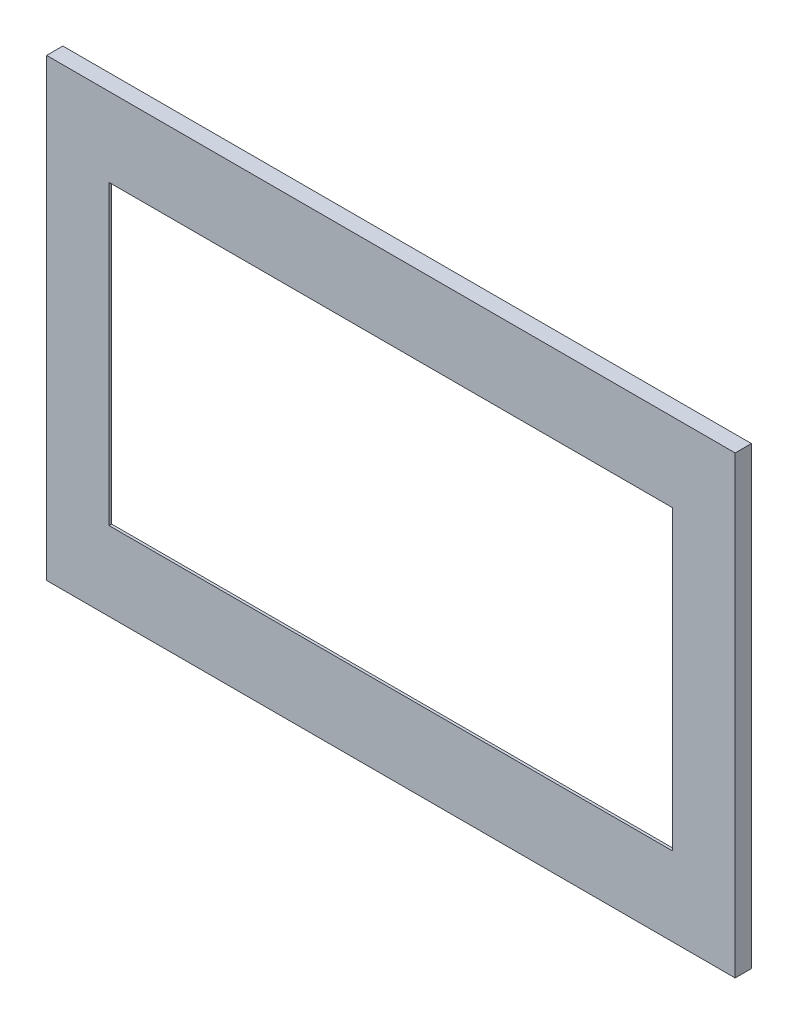
SolidWorks part; units mm, degrees
ref_plane "Front Plane" through (0, 0, 0) normal (0, 0, 1) x (1, 0, 0)
ref_plane "Top Plane" through (0, 0, 0) normal (0, 1, 0) x (1, 0, 0)
ref_plane "Right Plane" through (0, 0, 0) normal (1, 0, 0) x (0, 0, -1)
sketch "Sketch1" plane through (0, 0, 0) normal (0, 0, 1) x (1, 0, 0)
  line L1 (336.55, 222.25) -> (-336.55, 222.25)
  line L2 (336.55, 222.25) -> (336.55, -222.25)
  line L3 (336.55, -222.25) -> (-336.55, -222.25)
  line L4 (-336.55, 222.25) -> (-336.55, -222.25)
  line L5 (336.55, 222.25) -> (-336.55, -222.25) construction
  line L6 (336.55, -222.25) -> (-336.55, 222.25) construction
  point P0 (0, 0)
  dimension "D1" = 444.5
  dimension "D2" = 673.1
extrude "Boss-Extrude1" add sketch "Sketch1" along normal mid plane 15.875
sketch "Sketch2" plane through (0, 0, 7.9375) normal (0, 0, 1) x (1, 0, 0)
  line L0 (0, 0) -> (0, -222.25) construction
  line L1 (300.8312, 170.6562) -> (-300.8313, 170.6562)
  line L2 (300.8312, 170.6562) -> (300.8312, -170.6562)
  line L3 (300.8312, -170.6562) -> (-300.8313, -170.6562)
  line L4 (-300.8313, 170.6562) -> (-300.8313, -170.6562)
  line L5 (300.8312, 170.6562) -> (-300.8313, -170.6562) construction
  line L6 (300.8312, -170.6562) -> (-300.8313, 170.6562) construction
  line L7 (-336.55, -222.25) -> (336.55, -222.25) construction
  point P0 (0, 0)
  dimension "D1" = 341.3125
  dimension "D2" = 601.6625
extrude "Cut-Extrude1" cut sketch "Sketch2" against normal through all both and the other way through all
sketch "Sketch4" plane through (0, 0, 7.9375) normal (0, 0, 1) x (1, 0, 0)
  line L0 (-336.55, 222.25) -> (-336.55, -222.25) construction
  line L1 (-336.55, 203.2) -> (-344.4875, 203.2)
  line L2 (-336.55, 203.2) -> (-336.55, -203.2)
  line L3 (-336.55, -203.2) -> (-344.4875, -203.2)
  line L4 (-344.4875, 203.2) -> (-344.4875, -203.2)
  line L5 (336.55, -222.25) -> (336.55, 222.25) construction
  line L6 (336.55, 203.2) -> (344.4875, 203.2)
  line L7 (336.55, 203.2) -> (336.55, -203.2)
  line L8 (336.55, -203.2) -> (344.4875, -203.2)
  line L9 (344.4875, 203.2) -> (344.4875, -203.2)
  line L10 (336.55, 222.25) -> (-336.55, 222.25) construction
  line L15 (0, 0) -> (0, 230.1875) construction
  line L16 (-336.55, -222.25) -> (336.55, -222.25) construction
  dimension "D1" = 19.05
  dimension "D2" = 19.05
  dimension "D3" = 7.9375
  dimension "D4" = 688.975
extrude "Boss-Extrude2" [suppressed] add sketch "Sketch4" against normal up to surface (15.875 mm away) up to face at (0, 0, -7.9375)
fillet "Fillet1" [suppressed] radius 6.35
sketch "Sketch6" plane through (336.55, 0, 0) normal (1, 0, 0) x (0, 0, -1)
  line L0 (-7.9375, -222.25) -> (7.9375, -215.6744)
  line L2 (7.9375, -215.6744) -> (7.9375, -222.25)
  line L3 (7.9375, -222.25) -> (-7.9375, -222.25)
  dimension "D1" = 22.5
extrude "Cut-Extrude4" [suppressed] cut sketch "Sketch6" against normal through all both and the other way through all
sketch "Sketch7" plane through (0, 0, -7.9375) normal (0, 0, -1) x (-1, 0, 0)
  line L0 (0, 187.325) -> (0, -187.325) construction
  line L1 (-314.325, 0) -> (314.325, 0) construction
  line L2 (300.8313, -170.6562) -> (-300.8312, -170.6562) construction
  line L3 (-300.8312, 170.6562) -> (300.8313, 170.6562) construction
  line L15 (-307.975, -187.325) -> (307.975, -187.325)
  line L16 (314.325, -180.975) -> (314.325, 180.975)
  line L17 (307.975, 187.325) -> (-307.975, 187.325)
  line L18 (-314.325, 180.975) -> (-314.325, -180.975)
  arc A0 (314.325, 180.975) -> (307.975, 187.325) centre (307.975, 180.975) ccw
  arc A1 (307.975, -187.325) -> (314.325, -180.975) centre (307.975, -180.975) ccw
  arc A2 (-307.975, -187.325) -> (-314.325, -180.975) centre (-307.975, -180.975) cw
  arc A3 (-307.975, 187.325) -> (-314.325, 180.975) centre (-307.975, 180.975) ccw
  dimension "D2" = 6.35
  dimension "D1" = 628.65
  dimension "D3" = 374.65
  dimension "D4" = 16.6688
  dimension "D5" = 16.6687
extrude "Cut-Extrude5" [suppressed] cut sketch "Sketch7" against normal blind 9.525
sketch "Sketch8" plane through (0, 0, 7.9375) normal (0, 0, 1) x (1, 0, 0)
  line L0 (300.8312, -170.6562) -> (-300.8313, -170.6562) construction
  line L1 (300.8312, 170.6562) -> (-300.8313, 170.6562)
  line L2 (300.8312, 170.6562) -> (300.8312, -170.6562)
  line L3 (300.8312, -170.6562) -> (-300.8313, -170.6562)
  line L4 (-300.8313, 170.6562) -> (-300.8313, -170.6562)
  line L5 (-300.8313, 170.6562) -> (300.8312, 170.6562) construction
  line L6 (300.8312, 170.6562) -> (300.8312, -170.6562) construction
  line L8 (275.4312, 145.2562) -> (-275.4313, 145.2562)
  line L9 (275.4312, 145.2562) -> (275.4312, -145.2562)
  line L10 (275.4312, -145.2562) -> (-275.4313, -145.2562)
  line L11 (-275.4313, 145.2562) -> (-275.4313, -145.2562)
  point P0 (0, 0)
  point P8 (0, 3.81)
  point P15 (0, 170.6562)
  dimension "D1" = 25.4
  dimension "D2" = 25.4
  dimension "D3" = 25.4
  dimension "D4" = 25.4
extrude "Boss-Extrude3" add sketch "Sketch8" against normal blind 2.54
sketch "Sketch9" [suppressed] plane through (0, 0, 7.9375) normal (0, 0, 1) x (1, 0, 0)
  line L8 (-319.8813, -184.15) -> (319.8812, -184.15)
  line L9 (319.8812, -184.15) -> (319.8812, 195.2625)
  line L10 (319.8812, 195.2625) -> (-319.8813, 195.2625)
  line L11 (-319.8813, 195.2625) -> (-319.8813, -184.15)
  line L12 (-319.8813, -184.15) -> (319.8812, -184.15)
  line L13 (319.8812, -184.15) -> (319.8812, 195.2625)
  line L14 (319.8812, 195.2625) -> (-319.8813, 195.2625)
  line L15 (-319.8813, 195.2625) -> (-319.8813, -184.15)
  dimension "D1" = 19.05
sketch "Sketch10" [suppressed] plane through (0, 0, -7.9375) normal (0, 0, -1) x (-1, 0, 0)
  line L0 (-300.8312, 176.2125) -> (300.8313, 176.2125) construction
  line L1 (300.8313, 176.2125) -> (300.8313, -165.1) construction
  line L2 (-300.8312, -165.1) -> (-300.8312, 176.2125) construction
  line L3 (300.8313, -165.1) -> (-300.8312, -165.1) construction
  line L4 (-300.8312, 176.2125) -> (300.8313, 176.2125)
  line L5 (300.8313, 176.2125) -> (300.8313, -165.1)
  line L6 (-300.8312, -165.1) -> (-300.8312, 176.2125)
  line L7 (300.8313, -165.1) -> (-300.8312, -165.1)
loft "Cut-Loft1" [suppressed] cut profiles "Sketch9", "Sketch10"
